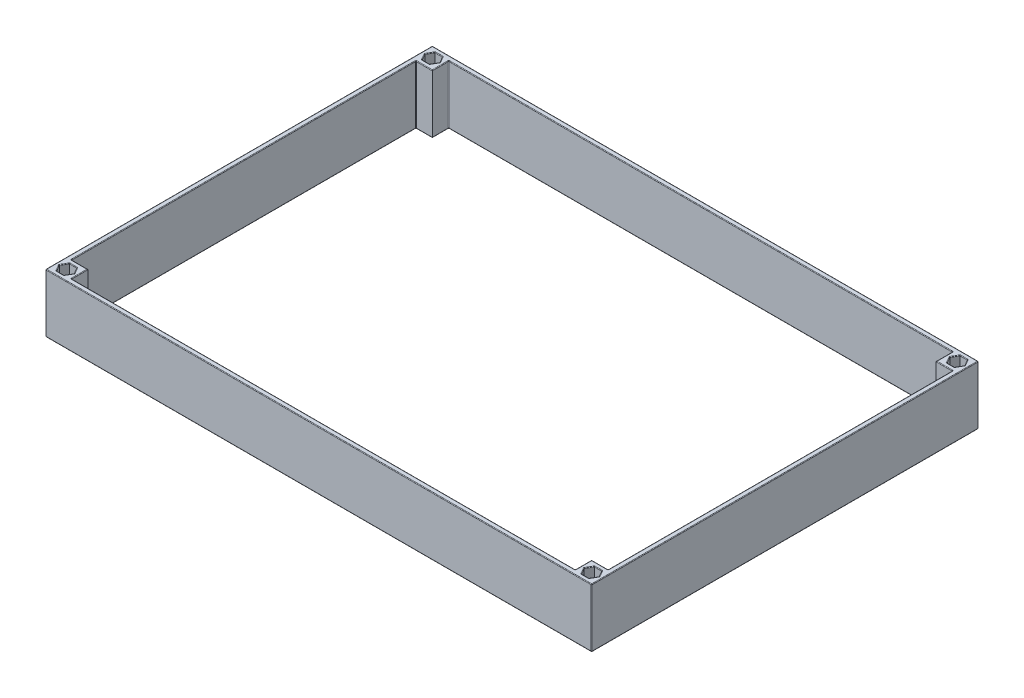
SolidWorks part; units mm, degrees
note: The reader was unsure of these and kept them because the rebuilt part matched: shared geometry of "Sketch1<3>".
ref_plane "Front Plane" through (0, 0, 0) normal (0, 0, 1) x (1, 0, 0)
ref_plane "Top Plane" through (0, 0, 0) normal (0, 1, 0) x (1, 0, 0)
ref_plane "Right Plane" through (0, 0, 0) normal (1, 0, 0) x (0, 0, -1)
sketch "Sketch1" plane through (0, 0, 0) normal (0, 1, 0) x (1, 0, 0)
  line L0 (0, 156) -> (9, 156)
  line L1 (2, 156) -> (2, 9)
  line L2 (9, 2) -> (224, 2)
  line L3 (231, 9) -> (231, 156)
  line L5 (7.6754, 160.5) -> (6.0877, 163.25)
  line L6 (6.0877, 163.25) -> (2.9123, 163.25)
  line L7 (0, 165) -> (233, 165)
  line L8 (0, 165) -> (0, 0)
  line L9 (0, 0) -> (233, 0)
  line L10 (233, 165) -> (233, 0)
  line L11 (9, 156) -> (9, 165)
  line L12 (0, 9) -> (9, 9)
  line L13 (9, 9) -> (9, 0)
  line L14 (224, 0) -> (224, 9)
  line L15 (224, 9) -> (233, 9)
  line L16 (233, 156) -> (224, 156)
  line L17 (224, 156) -> (224, 165)
  line L18 (2.9123, 163.25) -> (1.3246, 160.5)
  line L19 (9, 156) -> (0, 165) construction
  line L20 (224, 156) -> (233, 165) construction
  line L21 (9, 9) -> (0, 0) construction
  line L22 (224, 9) -> (233, 0) construction
  line L23 (1.3246, 160.5) -> (2.9123, 157.75)
  line L24 (2.9123, 157.75) -> (6.0877, 157.75)
  line L25 (6.0877, 157.75) -> (7.6754, 160.5)
  line L34 (231.6754, 160.5) -> (230.0877, 163.25)
  line L35 (0, 0) -> (233, 0) construction
  line L36 (0, 0) -> (0, 50) construction
  line L37 (230.0877, 163.25) -> (226.9123, 163.25)
  line L38 (233, 0) -> (233, 50) construction
  line L39 (224, 163) -> (9, 163)
  line L40 (226.9123, 163.25) -> (225.3246, 160.5)
  line L41 (225.3246, 160.5) -> (226.9123, 157.75)
  line L42 (226.9123, 157.75) -> (230.0877, 157.75)
  line L43 (230.0877, 157.75) -> (231.6754, 160.5)
  line L44 (231.6754, 4.5) -> (230.0877, 7.25)
  line L45 (230.0877, 7.25) -> (226.9123, 7.25)
  line L46 (226.9123, 7.25) -> (225.3246, 4.5)
  line L47 (225.3246, 4.5) -> (226.9123, 1.75)
  line L48 (226.9123, 1.75) -> (230.0877, 1.75)
  line L49 (230.0877, 1.75) -> (231.6754, 4.5)
  line L50 (7.6754, 4.5) -> (6.0877, 7.25)
  line L51 (6.0877, 7.25) -> (2.9123, 7.25)
  line L52 (2.9123, 7.25) -> (1.3246, 4.5)
  line L53 (1.3246, 4.5) -> (2.9123, 1.75)
  line L54 (2.9123, 1.75) -> (6.0877, 1.75)
  line L55 (6.0877, 1.75) -> (7.6754, 4.5)
  circle A0 centre (4.5, 160.5) radius 1.75
  circle A1 centre (228.5, 160.5) radius 1.75
  circle A2 centre (228.5, 4.5) radius 1.75
  circle A3 centre (4.5, 4.5) radius 1.75
  circle A4 centre (4.5, 160.5) radius 2.75 construction
  circle A5 centre (228.5, 160.5) radius 2.75 construction
  circle A6 centre (228.5, 4.5) radius 2.75 construction
  circle A7 centre (4.5, 4.5) radius 2.75 construction
  point P31 (7.6754, 160.5)
  dimension "D5" = 3.5
  dimension "D8" = 5.5
  dimension "D1" = 215
  dimension "D2" = 165
  dimension "D3" = 9
  dimension "D4" = 2
  dimension "D6" = 2
  dimension "D7" = 2
  dimension "D11" = 50
  dimension "D13" = 2
extrude "Boss-Extrude1" add sketch "Sketch1" along normal blind 5 contours L0 L11 L7 L8 A0 | L8 L12 L1 L0 | L39 L17 L7 L11 | L13 L12 L8 L9 A3 | L9 L14 L2 L13 | L10 L16 L3 L15 | L15 L14 L9 L10 A2 | L17 L16 L10 L7 A1
extrude "Boss-Extrude3" add sketch "Sketch1<3>" against normal blind 20 contours L10 L16 L3 L15 | L17 L16 L10 L7 L43 L42 L41 L40 L37 L34 | L39 L17 L7 L11 | L0 L11 L7 L8 L25 L24 L23 L18 L6 L5 | L24 L25 L5 L6 L18 L23 A0 | L8 L12 L1 L0 | L42 L43 L34 L37 L40 L41 A1 | L15 L14 L9 L10 L49 L48 L47 L46 L45 L44 | L48 L49 L44 L45 L46 L47 A2 | L9 L14 L2 L13 | L13 L12 L8 L9 L55 L54 L53 L52 L51 L50 | L54 L55 L50 L51 L52 L53 A3
sketch "Sketch1<3>" plane through (0, 0, 0) normal (0, 1, 0) x (1, 0, 0) same geometry as "Sketch1"
fillet "Fillet1" radius 0.25 68 edges at (224, 5, -5.5) (116.5, 5, 0) (233, 5, -82.5) (116.5, 5, -165) (0, 5, -82.5) (230.8816, 5, -159.125) (116.5, -20, 0) (0, -20, -82.5) (228.5, 5, -157.75) (9, -20, -159.5) (5.5, -20, -156) (2, -20, -82.5) (5.5, -20, -9) (9, -20, -5.5) (226.1184, 5, -159.125) (116.5, -20, -2) (224, -20, -5.5) (227.5, -20, -9) (231, -20, -82.5) (227.5, -20, -156) (224, -20, -159.5) (116.5, -20, -163) (233, -20, -82.5) (116.5, -20, -165) (228.5, -20, -2.75) (228.5, -20, -158.75) (4.5, -20, -2.75) (4.5, -20, -158.75) (226.1184, 5, -161.875) (116.5, 5, -2) (230.8816, 5, -161.875) (6.8816, 5, -3.125) (2.1184, 5, -3.125) (2.1184, 5, -5.875) (4.5, 5, -7.25) (6.8816, 5, -5.875) (230.8816, 5, -3.125) (226.1184, 5, -3.125) (9, 5, -5.5) (226.1184, 5, -5.875) (228.5, 5, -7.25) (230.8816, 5, -5.875) (5.5, 5, -9) (2, 5, -82.5) (5.5, 5, -156) (9, 5, -159.5) (116.5, 5, -163) (224, 5, -159.5) (227.5, 5, -156) (231, 5, -82.5) (227.5, 5, -9) (6.8816, 5, -159.125) (4.5, 5, -157.75) (0, -7.5, 0) (0, -7.5, -165) (233, -7.5, -165) (233, -7.5, 0) (2.1184, 5, -159.125) (231, -7.5, -9) (231, -7.5, -156) (224, -7.5, -163) (9, -7.5, -163) (2, -7.5, -156) (2, -7.5, -9) (9, -7.5, -2) (224, -7.5, -2) (2.1184, 5, -161.875) (6.8816, 5, -161.875)
